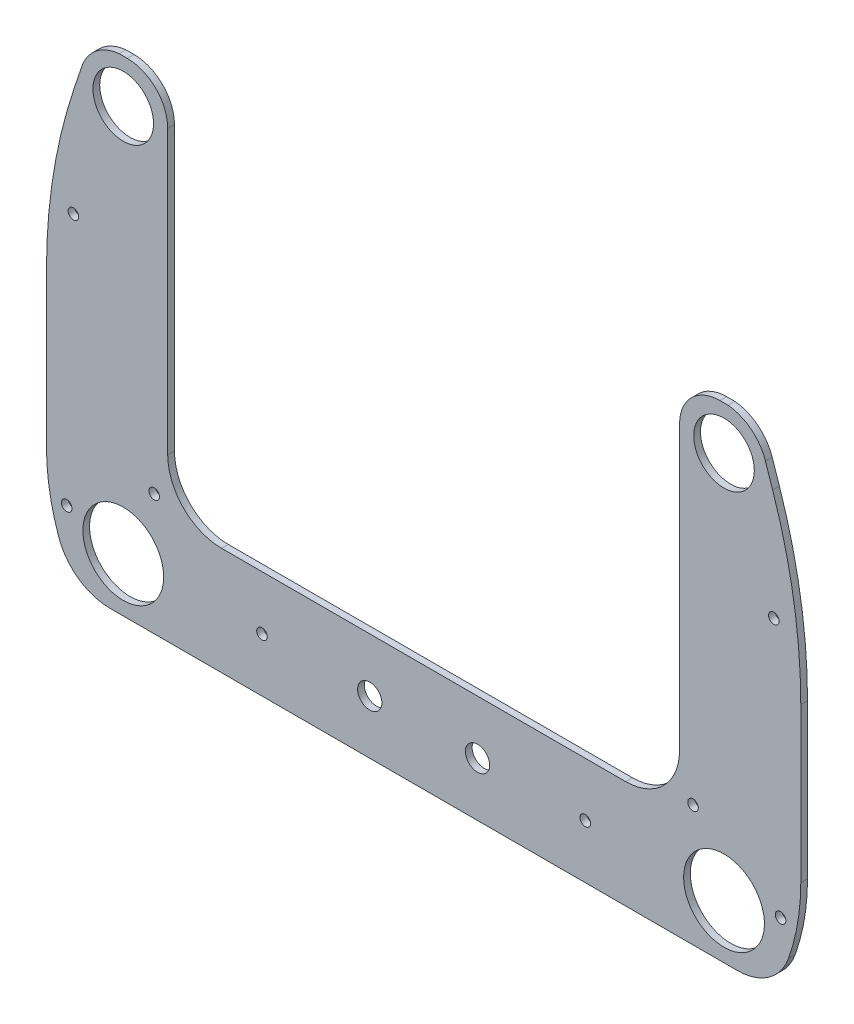
SolidWorks part; units mm, degrees
material "6061 Alloy"
ref_plane "Front Plane" through (0, 0, 0) normal (0, 0, 1) x (1, 0, 0)
ref_plane "Top Plane" through (0, 0, 0) normal (0, 1, 0) x (1, 0, 0)
ref_plane "Right Plane" through (0, 0, 0) normal (1, 0, 0) x (0, 0, -1)
sketch "Sketch1" plane through (0, 0, 0) normal (0, 0, 1) x (1, 0, 0)
  line L5 (120.65, -152.4) -> (120.65, -6.35)
  line L6 (127, 0) -> (171.45, 0) construction
  line L7 (177.8, -6.35) -> (177.8, -222.25)
  line L10 (0, -206.2199) -> (0, -63.6275) construction
  line L11 (-54.9244, 0) -> (300.6756, 0) construction
  line L13 (12.7, -177.8) -> (95.25, -177.8)
  line L14 (12.7, -228.6) -> (171.45, -228.6)
  line L15 (141.605, -20.5029) -> (141.605, -79.3851) construction
  line L16 (141.605, -20.5029) -> (141.605, -122.1029) construction
  line L19 (-141.605, -19.05) -> (-141.605, -77.9322) construction
  line L20 (141.605, -20.5029) -> (141.605, -203.2) construction
  line L22 (-120.65, -152.4) -> (-120.65, -6.35)
  line L23 (-12.7, -177.8) -> (-95.25, -177.8)
  line L24 (-12.7, -228.6) -> (-171.45, -228.6)
  line L25 (-177.8, -6.35) -> (-177.8, -222.25)
  line L26 (-12.7, -177.8) -> (12.7, -177.8)
  line L27 (-12.7, -228.6) -> (12.7, -228.6)
  line L28 (-177.8, -6.35) -> (-177.8, 6.35)
  line L29 (-165.1, 19.05) -> (-133.35, 19.05)
  line L30 (-120.65, 6.35) -> (-120.65, -6.35)
  line L31 (120.65, 6.35) -> (120.65, -6.35)
  line L32 (177.8, -6.35) -> (177.8, 6.35)
  line L33 (165.1, 19.05) -> (133.35, 19.05)
  arc A0 (95.25, -177.8) -> (120.65, -152.4) centre (95.25, -152.4) ccw
  arc A4 (120.65, -6.35) -> (127, 0) centre (127, -6.35) cw construction
  circle A8 centre (141.605, -20.5029) radius 14.2875
  circle A9 centre (141.605, -20.5029) radius 38.1 construction
  arc A10 (177.8, -6.35) -> (171.45, 0) centre (171.45, -6.35) ccw construction
  arc A11 (171.45, -228.6) -> (177.8, -222.25) centre (171.45, -222.25) ccw
  arc A14 (141.605, -77.6529) -> (120.9214, -73.7787) centre (141.605, -20.5029) ccw construction
  arc A15 (-141.605, -77.6529) -> (-120.9214, -73.7787) centre (-141.605, -20.5029) cw construction
  circle A16 centre (-141.605, -20.5029) radius 38.1 construction
  circle A17 centre (-141.605, -20.5029) radius 14.2875
  arc A19 (-95.25, -177.8) -> (-120.65, -152.4) centre (-95.25, -152.4) cw
  circle A20 centre (141.605, -122.1029) radius 38.1 construction
  circle A21 centre (-141.605, -122.1029) radius 38.1 construction
  arc A23 (-171.45, -228.6) -> (-177.8, -222.25) centre (-171.45, -222.25) cw
  circle A24 centre (-141.605, -203.2) radius 19.05
  circle A37 centre (141.605, -203.2) radius 19.05
  circle A39 centre (-76.2, -203.2) radius 2.4892
  circle A40 centre (76.2, -203.2) radius 2.4892
  circle A42 centre (-25.4, -203.2) radius 5.715
  arc A44 (-133.35, 19.05) -> (-120.65, 6.35) centre (-133.35, 6.35) cw
  arc A45 (-177.8, 6.35) -> (-165.1, 19.05) centre (-165.1, 6.35) cw
  arc A46 (133.35, 19.05) -> (120.65, 6.35) centre (133.35, 6.35) ccw
  arc A47 (177.8, 6.35) -> (165.1, 19.05) centre (165.1, 6.35) ccw
  circle A50 centre (-149.225, 6.35) radius 2.4892
  circle A53 centre (149.225, 6.35) radius 2.4892
  circle A54 centre (-168.275, -196.85) radius 2.4892
  circle A56 centre (168.275, -196.85) radius 2.4892
  circle A58 centre (-165.1, -76.2) radius 2.4892
  circle A59 centre (165.1, -76.2) radius 2.4892
  circle A60 centre (-127, -171.45) radius 2.4892
  circle A61 centre (127, -171.45) radius 2.4892
  circle A62 centre (25.4, -203.2) radius 5.715
  point P2 (177.8, -44.45)
  point P18 (177.8, 0)
  point P23 (177.8, -228.6)
  point P24 (177.8, -228.6)
  point P31 (177.8, 0)
  point P48 (-177.8, 0)
  point P49 (-177.8, -228.6)
  point P51 (-177.8, -44.45)
  point P78 (-141.605, -203.2)
  dimension "D6" = 25.4
  dimension "D7" = 6.35
  dimension "D8" = 6.35
  dimension "D9" = 177.8
  dimension "D10" = 28.575
  dimension "D12" = 76.2
  dimension "D13" = 57.15
  dimension "D15" = 38.1
  dimension "D18" = 76.2
  dimension "D21" = 4.9784
  dimension "D29" = 9.525
  dimension "D32" = 4.9784
  dimension "D35" = 11.43
  dimension "D40" = 12.7
  dimension "D43" = 4.9784
  dimension "D45" = 12.7
  dimension "D30" = 4.9784
  dimension "D41" = 4.9784
  dimension "D22" = 6.35
  dimension "D2" = 120.65
  dimension "D3" = 177.8
  dimension "D4" = 228.6
  dimension "D5" = 177.8
  dimension "D11" = 20.955
  dimension "`" = 20.5029
  dimension "D14" = 57.15
  dimension "D16" = 184.15
  dimension "D17" = 101.6
  dimension "D19" = 25.4
  dimension "D20" = 101.6
  dimension "D23" = 57.15
  dimension "D25" = 25.4
  dimension "D26" = 31.75
  dimension "D27" = 25.4
  dimension "D28" = 25.4
  dimension "D31" = 25.4
  dimension "D33" = 12.7
  dimension "D34" = 25.4
  dimension "D39" = 19.05
  dimension "D44" = 28.575
  dimension "D24" = 95.25
extrude "Boss-Extrude3" add sketch "Sketch1" along normal blind 3.175
sketch "Sketch2" plane through (0, 0, 3.175) normal (0, 0, 1) x (1, 0, 0)
  line L0 (177.8, -222.25) -> (177.8, 6.35) construction
  line L1 (-177.8, 19.05) -> (177.8, 19.05)
  line L2 (-177.8, 19.05) -> (-177.8, 0)
  line L3 (-177.8, 0) -> (177.8, 0)
  line L4 (177.8, 19.05) -> (177.8, 0)
  line L5 (-177.8, 6.35) -> (-177.8, -222.25) construction
  line L7 (-133.35, 19.05) -> (-165.1, 19.05) construction
  dimension "D1" = 19.05
extrude "Cut-Extrude1" cut sketch "Sketch2" against normal through all
fillet "Fillet1" radius 19.05 4 edges at (177.8, 0, 1.5875) (120.65, 0, 1.5875) (-120.65, 0, 1.5875) (-177.8, 0, 1.5875)
sketch "Sketch3" plane through (0, 0, 3.175) normal (0, 0, 1) x (1, 0, 0)
  line L2 (-177.8, -19.05) -> (-177.8, -222.25) construction
  line L3 (-158.75, 0) -> (-139.7, 0) construction
  line L4 (-177.8, -63.5) -> (-177.8, 0)
  line L5 (-177.8, 0) -> (-139.7, 0)
  line L6 (-177.8, -63.5) -> (-161.1208, -13.9355)
  arc A3 (-139.7, 0) -> (-161.1208, -13.9355) centre (-141.605, -20.5029) ccw
  arc M14 (-158.75, 0) -> (-177.8, -19.05) centre (-158.75, -19.05) ccw
  line M15 (-177.8, -19.05) -> (-177.8, -222.25)
  dimension "D1" = 63.5
extrude "Cut-Extrude2" cut sketch "Sketch3" against normal through all contours A3 L5 M14 M15 | L5 L4 M14 region at (-169.3275, -22.1097, 3.175) region at (-173.5448, -4.2552, 3.175)
ref_plane "Plane1" through (0, 0, 0) normal (-1, 0, 0) x (0, 0, 1)
mirror "Mirror1" about plane through (0, 0, 0) normal (-1, 0, 0) of "Cut-Extrude2"
fillet "Fillet2" radius 254 2 edges at (177.8, -63.5, 1.5875) (-177.8, -63.5, 1.5875)
sketch "Sketch4" plane through (0, 0, 3.175) normal (0, 0, 1) x (1, 0, 0)
  line L0 (0, -177.8) -> (0, -13.685) construction
  line L5 (-177.8, -105.0915) -> (-177.8, -222.25) construction
  line L6 (-171.45, -228.6) -> (171.45, -228.6) construction
  line L7 (-177.8, -177.8) -> (-177.8, -228.6)
  line L8 (-177.8, -228.6) -> (-164.1882, -228.6)
  line L9 (177.8, -177.8) -> (177.8, -228.6)
  line L10 (177.8, -228.6) -> (164.1882, -228.6)
  circle A0 centre (-76.2, -177.8) radius 101.6 construction
  arc A1 (-177.8, -177.8) -> (-164.1882, -228.6) centre (-76.2, -177.8) ccw
  arc A2 (177.8, -177.8) -> (164.1882, -228.6) centre (76.2, -177.8) cw
  dimension "D1" = 203.2
  dimension "D2" = 50.8
extrude "Cut-Extrude3" cut sketch "Sketch4" against normal through all contours L8 A1 L7 | L9 L10 A2
fillet "Fillet3" radius 25.4 2 edges at (164.1882, -228.6, 1.5875) (-164.1882, -228.6, 1.5875)
